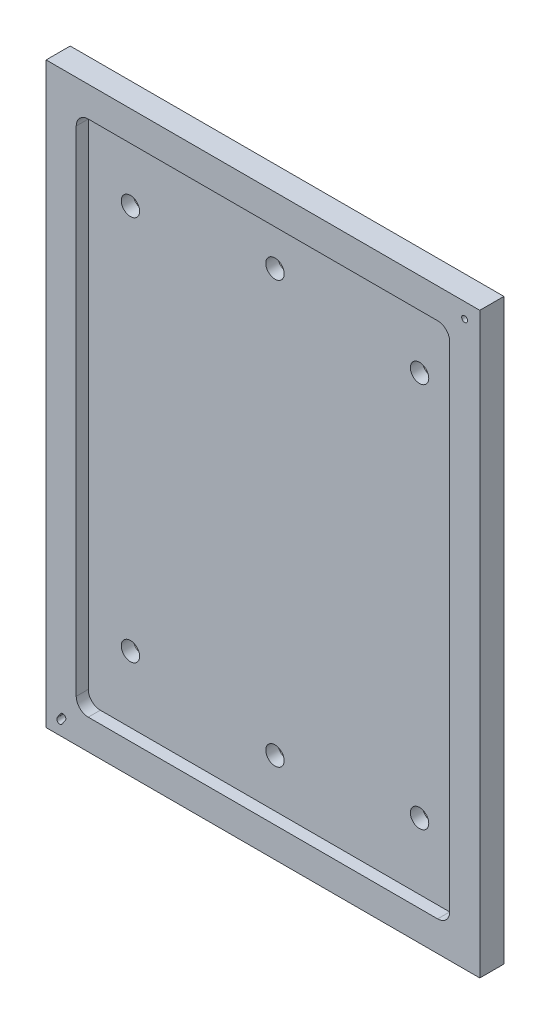
SolidWorks part; units mm, degrees
ref_plane "Front Plane" through (0, 0, 0) normal (0, 0, 1) x (1, 0, 0)
ref_plane "Top Plane" through (0, 0, 0) normal (0, 1, 0) x (1, 0, 0)
ref_plane "Right Plane" through (0, 0, 0) normal (1, 0, 0) x (0, 0, -1)
sketch "Sketch1" plane through (0, 0, 0) normal (0, 0, 1) x (1, 0, 0)
  line L1 (114.3, -152.4) -> (-114.3, -152.4)
  line L2 (114.3, -152.4) -> (114.3, 152.4)
  line L3 (114.3, 152.4) -> (-114.3, 152.4)
  line L4 (-114.3, -152.4) -> (-114.3, 152.4)
  line L5 (114.3, -152.4) -> (-114.3, 152.4) construction
  line L6 (114.3, 152.4) -> (-114.3, -152.4) construction
  point P0 (0, 0)
  dimension "D1" = 228.6
  dimension "D2" = 304.8
extrude "Boss-Extrude1" add sketch "Sketch1" along normal blind 12.7
sketch "Sketch2" plane through (0, 0, 12.7) normal (0, 0, 1) x (1, 0, 0)
  line L0 (-114.3, 152.4) -> (-114.3, -152.4) construction
  line L1 (92.075, -136.525) -> (-92.075, -136.525)
  line L2 (98.425, -130.175) -> (98.425, 130.175)
  line L3 (92.075, 136.525) -> (-92.075, 136.525)
  line L4 (-98.425, -130.175) -> (-98.425, 130.175)
  line L5 (98.425, -136.525) -> (-98.425, 136.525) construction
  line L6 (98.425, 136.525) -> (-98.425, -136.525) construction
  line L7 (114.3, 152.4) -> (-114.3, 152.4) construction
  arc A0 (-92.075, -136.525) -> (-98.425, -130.175) centre (-92.075, -130.175) cw
  arc A1 (92.075, -136.525) -> (98.425, -130.175) centre (92.075, -130.175) ccw
  arc A2 (98.425, 130.175) -> (92.075, 136.525) centre (92.075, 130.175) ccw
  arc A3 (-92.075, 136.525) -> (-98.425, 130.175) centre (-92.075, 130.175) ccw
  point P0 (0, 0)
  dimension "D3" = 6.35
  dimension "D1" = 15.875
  dimension "D2" = 15.875
extrude "Cut-Extrude1" cut sketch "Sketch2" against normal blind 6.35
sketch "Sketch4" plane through (0, 0, 6.35) normal (0, 0, 1) x (1, 0, 0)
  line L4 (-114.3, 152.4) -> (-114.3, -152.4) construction
  line L5 (114.3, -152.4) -> (114.3, 152.4) construction
  line L6 (-114.3, -152.4) -> (114.3, -152.4) construction
  line L7 (92.075, 136.525) -> (-92.075, 136.525) construction
  line L8 (-92.075, -136.525) -> (92.075, -136.525) construction
  circle A0 centre (-76.2, 101.6) radius 4.85
  circle A1 centre (76.2, 101.6) radius 4.85
  circle A2 centre (-76.2, -101.6) radius 4.85
  circle A3 centre (76.2, -101.6) radius 4.85
  circle A4 centre (0, 111.125) radius 4.85
  circle A5 centre (0, -111.125) radius 4.85
  point P8 (0, 0)
  point P9 (0, 0)
  dimension "D1" = 9.7
  dimension "D2" = 9.7
  dimension "D3" = 9.7
  dimension "D4" = 9.7
  dimension "D13" = 9.7
  dimension "D14" = 9.7
  dimension "D15" = 25.4
  dimension "D5" = 9.525
  dimension "D6" = 38.1
  dimension "D7" = 38.1
  dimension "D8" = 0
  dimension "D9" = 50.8
  dimension "D10" = 38.1
  dimension "D11" = 38.1
  dimension "D12" = 50.8
  dimension "D16" = 25.4
extrude "Cut-Extrude2" cut sketch "Sketch4" against normal through all
hole_wizard "Ø3.1 (3.1) Diameter Hole1" positions "Sketch5" profile "Sketch6" hole size "Ø3.1" standard "ANSI Metric"
sketch "Sketch5" plane through (0, 0, 12.7) normal (0, 0, 1) x (1, 0, 0)
  line L0 (114.3, 152.4) -> (-114.3, 152.4) construction
  line L1 (114.3, -152.4) -> (114.3, 152.4) construction
  point P0 (106.3, 144.4)
  dimension "D1" = 8
  dimension "D2" = 8
sketch "Sketch6" plane through (106.3, 144.4, 12.7) normal (1, 0, 0) x (0, -1, 0)
  line L0 (0, 0) -> (0, 5.9313)
  line L1 (0, 5.9313) -> (1.55, 5)
  line L2 (1.55, 5) -> (1.55, 0)
  line L5 (1.55, 0) -> (0, 0)
  line L10 (0, 5.9313) -> (-1.55, 5) construction
  line L11 (0, -6.35) -> (0, 107.95) construction
  dimension "Hole Dia." = 3.1
  dimension "Hole Depth" = 5
  dimension "Drill Angle" = 118
sketch "Sketch7" plane through (0, 0, 12.7) normal (0, 0, 1) x (1, 0, 0)
  line L0 (-107.1279, -145.6508) -> (-105.4721, -143.1492) construction
  line L1 (-108.4204, -144.7953) -> (-106.7646, -142.2937)
  line L2 (-105.8354, -146.5063) -> (-104.1796, -144.0047)
  line L3 (-114.3, -152.4) -> (114.3, -152.4) construction
  line L4 (-114.3, 152.4) -> (-114.3, -152.4) construction
  arc A0 (-108.4204, -144.7953) -> (-105.8354, -146.5063) centre (-107.1279, -145.6508) ccw
  arc A1 (-104.1796, -144.0047) -> (-106.7646, -142.2937) centre (-105.4721, -143.1492) ccw
  point P2 (-106.3, -144.4)
  point P7 (-107.5925, -143.5445)
  dimension "D1" = 3
  dimension "D2" = 3.1
  dimension "D3" = 8
  dimension "D4" = 8
  dimension "D5" = 56.5
extrude "Cut-Extrude3" cut sketch "Sketch7" against normal blind 5
hole_wizard "M4x0.7 Tapped Hole1" positions "Sketch8" profile "Sketch9" tap size "M4x0.7" standard "ANSI Metric"
sketch "Sketch8" plane through (0, 0, 0) normal (0, 0, -1) x (-1, 0, 0)
  line L0 (114.3, -152.4) -> (-114.3, -152.4) construction
  line L1 (-114.3, -152.4) -> (-114.3, 152.4) construction
  point P0 (-106.3, -102.4)
  point P2 (-106.3, 0)
  point P4 (-106.3, 113.6)
  point P14 (-114.3, 0)
  dimension "D1" = 266
  dimension "D2" = 8
  dimension "D3" = 50
cosmetic thread "Hole Thread1" parameters "D1"=3, "D2"=4
cosmetic thread "Hole Thread2" parameters "D1"=3, "D2"=4
cosmetic thread "Hole Thread3" parameters "D1"=3, "D2"=4
sketch "Sketch9" plane through (106.3, -102.4, 0) normal (1, 0, 0) x (0, 1, 0)
  line L0 (0, 0) -> (0, 6.3914)
  line L1 (0, 6.3914) -> (1.65, 5.4)
  line L2 (1.65, 5.4) -> (1.65, 0)
  line L5 (1.65, 0) -> (0, 0)
  line L10 (0, 6.3914) -> (-1.65, 5.4) construction
  line L11 (0, -6.35) -> (0, 107.95) construction
  dimension "Tap Drill Dia." = 3.3
  dimension "Tap Drill Depth" = 5.4
  dimension "Drill Angle" = 118
